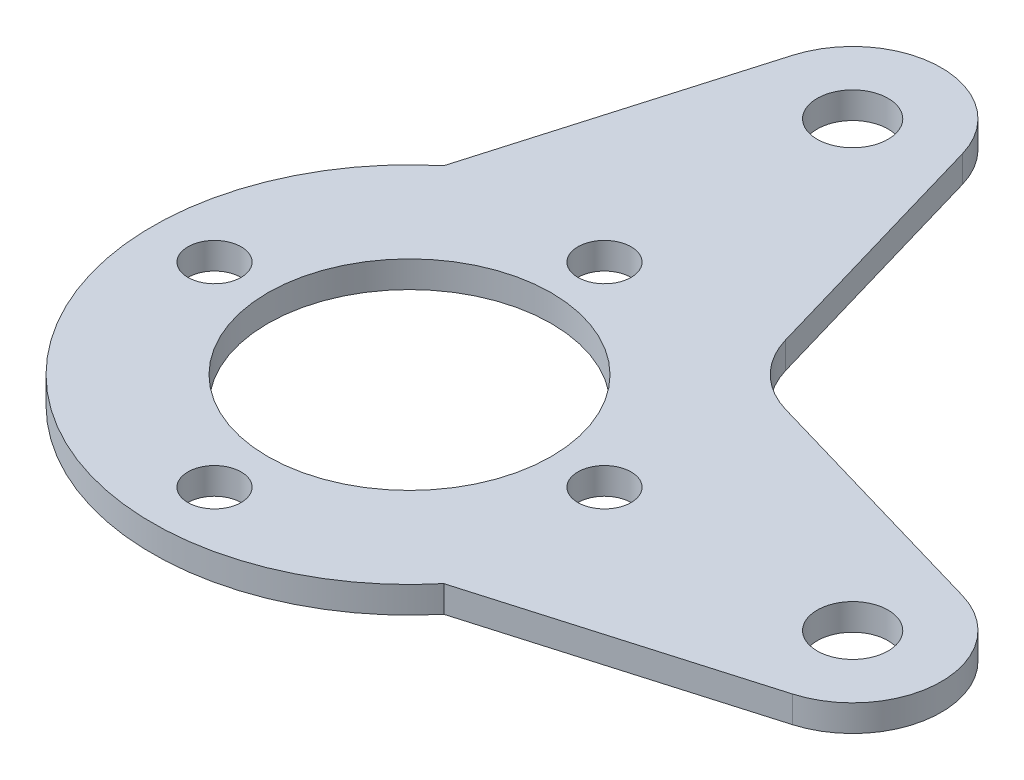
SolidWorks part; units mm, degrees
material "ABS PC"
ref_plane "Płaszczyzna przednia" through (0, 0, 0) normal (0, 0, 1) x (1, 0, 0)
ref_plane "Płaszczyzna górna" through (0, 0, 0) normal (0, 1, 0) x (1, 0, 0)
ref_plane "Płaszczyzna prawa" through (0, 0, 0) normal (1, 0, 0) x (0, 0, -1)
sketch "Szkic1" plane through (0, 0, 0) normal (0, 1, 0) x (1, 0, 0)
  line L6 (62.5088, 30.2454) -> (92.9611, 39.1274)
  line L7 (64.7805, 66.5467) -> (92.9611, 58.3274)
  line L8 (57.9805, 73.3467) -> (49.7611, 101.5274)
  line L9 (21.6792, 71.075) -> (30.5611, 101.5274)
  arc A14 (92.9611, 39.1274) -> (92.9611, 58.3274) centre (90.1611, 48.7274) ccw
  arc A15 (57.9805, 73.3467) -> (64.7805, 66.5467) centre (67.5805, 76.1467) ccw
  arc A16 (49.7611, 101.5274) -> (30.5611, 101.5274) centre (40.1611, 98.7274) ccw
  circle A17 centre (40.1611, 98.7274) radius 4
  circle A18 centre (90.1611, 48.7274) radius 4
  circle A19 centre (40.1611, 48.7274) radius 16
  circle A20 centre (40.1611, 70.7274) radius 3
  circle A21 centre (18.1611, 48.7274) radius 3
  circle A22 centre (40.1611, 26.7274) radius 3
  circle A23 centre (62.1611, 48.7274) radius 3
  arc A24 (21.6792, 71.075) -> (62.5088, 30.2454) centre (40.1611, 48.7274) ccw
extrude "Dodanie-wyciągnięcie1" add sketch "Szkic1" along normal blind 3
